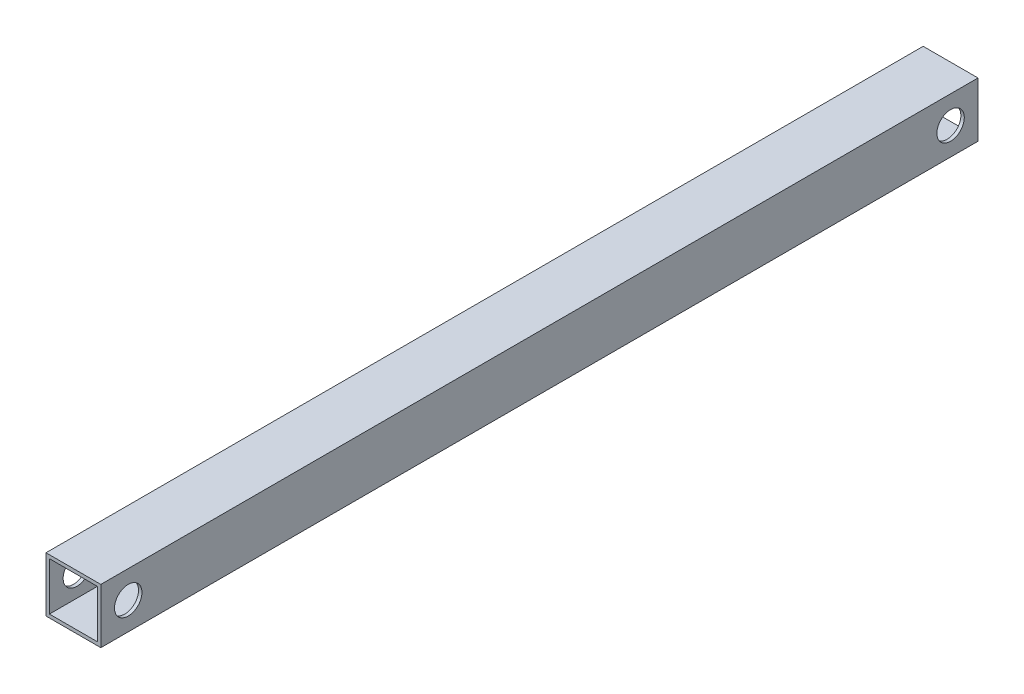
SolidWorks part; units mm, degrees
ref_plane "Front Plane" through (0, 0, 0) normal (0, 0, 1) x (1, 0, 0)
ref_plane "Top Plane" through (0, 0, 0) normal (0, 1, 0) x (1, 0, 0)
ref_plane "Right Plane" through (0, 0, 0) normal (1, 0, 0) x (0, 0, -1)
sketch "Sketch1" plane through (0, 0, 0) normal (0, 0, 1) x (1, 0, 0)
  line L1 (12.7, -12.7) -> (-12.7, -12.7)
  line L2 (12.7, -12.7) -> (12.7, 12.7)
  line L3 (12.7, 12.7) -> (-12.7, 12.7)
  line L4 (-12.7, -12.7) -> (-12.7, 12.7)
  line L5 (12.7, -12.7) -> (-12.7, 12.7) construction
  line L6 (12.7, 12.7) -> (-12.7, -12.7) construction
  point P0 (0, 0)
  dimension "D1" = 25.4
extrude "Extrude-Thin1" add sketch "Sketch1" along normal mid plane 406.4 thin thin type one direction reverse wall 1.5875
sketch "Sketch2" plane through (12.7, 0, 0) normal (1, 0, 0) x (0, 0, -1)
  line L0 (-190.5, 12.7) -> (-190.5, 0) construction
  line L1 (-203.2, 12.7) -> (203.2, 12.7) construction
  line L2 (-190.5, 0) -> (-190.5, -12.7) construction
  line L3 (-203.2, -12.7) -> (203.2, -12.7) construction
  line L4 (-203.2, -12.7) -> (-203.2, 12.7) construction
  line L5 (0, 12.7) -> (0, -12.7) construction
  line L6 (190.5, 0) -> (190.5, -12.7) construction
  line L7 (190.5, 12.7) -> (190.5, 0) construction
  circle A0 centre (-190.5, 0) radius 6.35
  circle A1 centre (190.5, 0) radius 6.35
  dimension "D1" = 12.7
  dimension "D2" = 12.7
extrude "Cut-Extrude1" cut sketch "Sketch2" against normal through all
